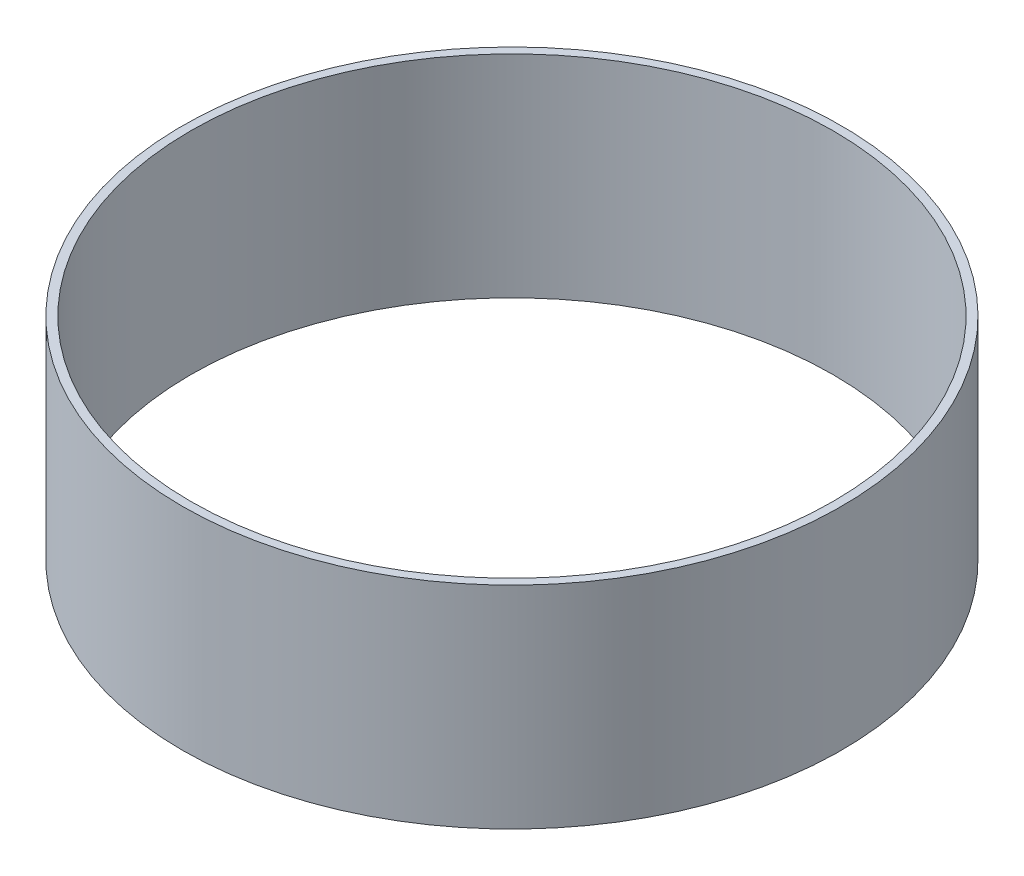
SolidWorks part; units mm, degrees
material "A-Glass Fiber"
ref_plane "Front Plane" through (0, 0, 0) normal (0, 0, 1) x (1, 0, 0)
ref_plane "Top Plane" through (0, 0, 0) normal (0, 1, 0) x (1, 0, 0)
ref_plane "Right Plane" through (0, 0, 0) normal (1, 0, 0) x (0, 0, -1)
sketch "Sketch1" plane through (0, 0, 0) normal (0, 1, 0) x (1, 0, 0)
  circle A0 centre (0, 0) radius 76
  circle A1 centre (0, 0) radius 78
  dimension "D1" = 152
  dimension "D2" = 2
extrude "Boss-Extrude1" add sketch "Sketch1" along normal blind 25 and the other way blind 25
